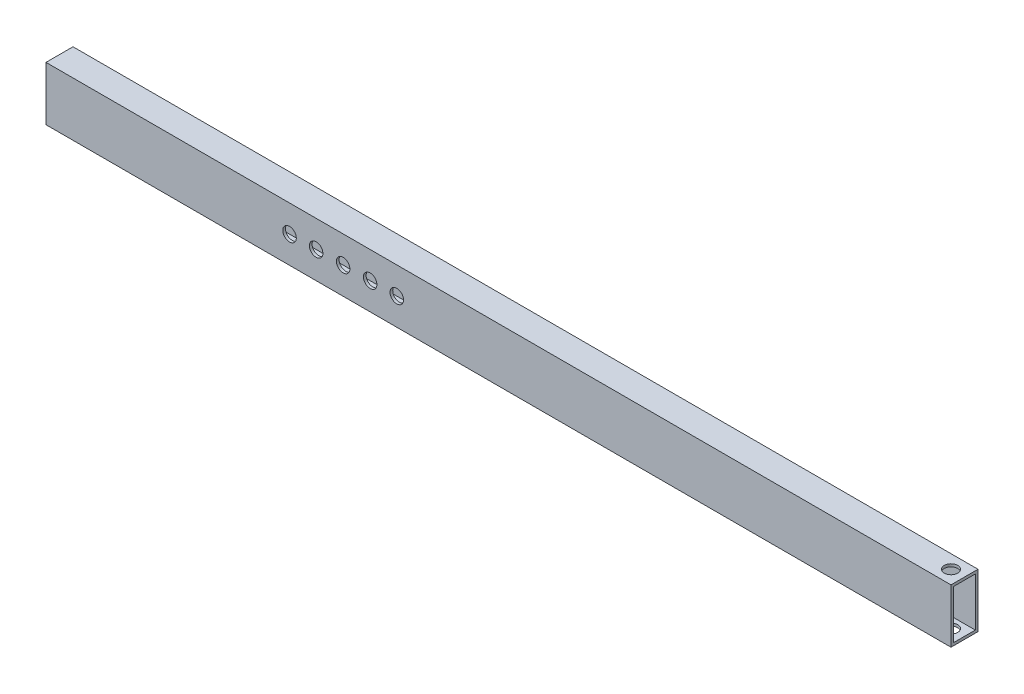
SolidWorks part; units mm, degrees
ref_plane "Front Plane" through (0, 0, 0) normal (0, 0, 1) x (1, 0, 0)
ref_plane "Top Plane" through (0, 0, 0) normal (0, 1, 0) x (1, 0, 0)
ref_plane "Right Plane" through (0, 0, 0) normal (1, 0, 0) x (0, 0, -1)
sketch "Sketch1" plane through (0, 0, 0) normal (1, 0, 0) x (0, 0, -1)
  line L0 (-4, -9) -> (-4, 9)
  line L1 (-5, -10) -> (5, -10)
  line L2 (-5, -10) -> (-5, 10)
  line L3 (-5, 10) -> (5, 10)
  line L4 (5, -10) -> (5, 10)
  line L5 (-5, -10) -> (5, 10) construction
  line L6 (-5, 10) -> (5, -10) construction
  line L7 (-4, 9) -> (4, 9)
  line L8 (4, -9) -> (4, 9)
  line L9 (-4, -9) -> (4, -9)
  point P0 (0, 0)
  dimension "D1" = 20
  dimension "D2" = 10
  dimension "D3" = 1
extrude "Boss-Extrude1" add sketch "Sketch1" along normal blind 225 and the other way blind 110
sketch "Sketch2" plane through (0, 0, 5) normal (0, 0, 1) x (1, 0, 0)
  line L0 (0, -10) -> (0, 10) construction
  line L1 (-110, -10) -> (225, -10) construction
  line L2 (-110, 10) -> (225, 10) construction
  circle A0 centre (-19.85, 0) radius 2.5
  circle A1 centre (-10, 0) radius 2.5
  circle A2 centre (0, 0) radius 2.5
  circle A3 centre (19.85, 0) radius 2.5
  circle A4 centre (10, 0) radius 2.5
  dimension "D5" = 5
  dimension "D6" = 5
  dimension "D7" = 5
  dimension "D1" = 10
  dimension "D3" = 9.85
  dimension "D4" = 10
  dimension "D8" = 9.85
  dimension "D9" = 10
extrude "Cut-Extrude1" cut sketch "Sketch2" against normal blind 1
sketch "Sketch3" plane through (0, 10, 0) normal (0, 1, 0) x (1, 0, 0)
  line L0 (225, 5) -> (225, -5) construction
  line L1 (-110, 5) -> (225, 5) construction
  line L2 (-110, -5) -> (225, -5) construction
  line L3 (-110, 5) -> (-110, -5) construction
  circle A0 centre (220, 0) radius 2.5
  circle A1 centre (-105, 0) radius 2.5 construction
  point P4 (225, 0)
  dimension "D3" = 5
  dimension "D4" = 5
  dimension "D1" = 5
  dimension "D2" = 5
  dimension "D5" = 5
  dimension "D6" = 5
extrude "Cut-Extrude2" cut sketch "Sketch3" against normal blind 20
